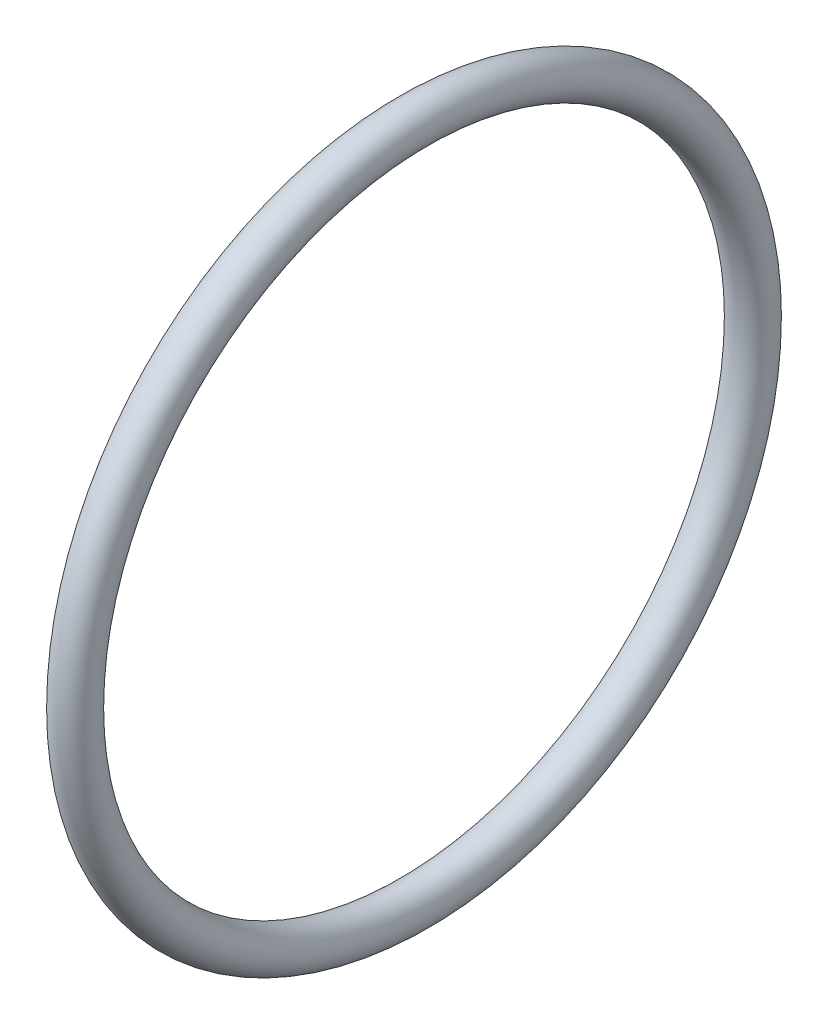
SolidWorks part; units mm, degrees
ref_plane "Front Plane" through (0, 0, 0) normal (0, 0, 1) x (1, 0, 0)
ref_plane "Top Plane" through (0, 0, 0) normal (0, 1, 0) x (1, 0, 0)
ref_plane "Right Plane" through (0, 0, 0) normal (1, 0, 0) x (0, 0, -1)
sketch "Sketch2" plane through (0, 0, 0) normal (0, 0, 1) x (1, 0, 0)
  line L0 (0, 0) -> (58.591, 0) construction
  line L2 (0, 0) -> (18.4, 0)
  line L3 (0, 0) -> (0, 2.5)
  line L4 (0, 2.5) -> (18.4, 2.5)
  line L5 (18.4, 0) -> (18.4, 2.5)
  line L6 (6, 2.5) -> (6, 6)
  line L11 (6, 6) -> (9.97, 6)
  line L16 (12.97, 6) -> (12.97, 3)
  line L17 (12.97, 3) -> (13.6304, 3)
  line L18 (13.6304, 3) -> (13.6304, 2.5)
  line L19 (13.6304, 2.5) -> (6, 2.5)
  line L22 (13.6304, 2.5) -> (16.1104, 2.5)
  line L23 (13.6304, 2.5) -> (13.6304, 4)
  line L24 (13.6304, 4) -> (16.1104, 4)
  line L25 (16.1104, 2.5) -> (16.1104, 4)
  line L27 (6, 6) -> (9.97, 6)
  line L28 (6, 6) -> (6, 9)
  line L29 (6, 9) -> (9.97, 9)
  line L30 (9.97, 6) -> (9.97, 9)
  line L31 (6, 9) -> (6, 8.25)
  line L32 (6, 8.25) -> (5, 8.25)
  line L33 (8.58, 22.001) -> (8.58, 12.476) construction
  line L34 (5, 12.476) -> (12.16, 12.476)
  line L35 (9.97, 9) -> (12.16, 9)
  line L36 (5, 7.5) -> (3, 7.5)
  line L37 (5, 8.25) -> (5, 12.476)
  line L38 (5, 7.5) -> (5, 14)
  line L39 (5, 14) -> (3, 14)
  line L40 (3, 7.5) -> (3, 14)
  line L41 (5, 22.001) -> (12.16, 22.001)
  line L42 (5, 22.001) -> (5, 30.1625)
  line L43 (5, 30.1625) -> (12.16, 30.1625)
  line L44 (12.16, 22.001) -> (12.16, 30.1625)
  line L49 (16.6304, 22.001) -> (16.6304, 7.5)
  line L51 (23.0104, 7.5) -> (23.0104, 6.5)
  line L54 (16.1104, 4) -> (13.6304, 4)
  line L56 (18.0304, 7.5) -> (23.0104, 7.5)
  line L57 (13.16, 22.001) -> (16.6304, 22.001)
  line L58 (16.1104, 3.5) -> (20.0104, 3.5)
  line L59 (29.9004, 14) -> (26.9004, 11)
  line L60 (4, 31.75) -> (18.0304, 31.75)
  line L61 (18.0304, 7.5) -> (23.0104, 7.5)
  line L62 (18.0304, 7.5) -> (18.0304, 12)
  line L63 (18.0304, 12) -> (23.0104, 12)
  line L64 (23.0104, 7.5) -> (23.0104, 12)
  line L65 (18.0304, 31.75) -> (18.0304, 12)
  line L66 (23.0104, 11) -> (26.9004, 11)
  line L67 (34.8004, 23) -> (31.3004, 19.5)
  line L68 (35.8004, 31) -> (38.7904, 33.99)
  line L69 (29.9004, 14) -> (29.9004, 15)
  line L70 (29.9004, 15) -> (22.9304, 15)
  line L71 (22.9304, 15) -> (21.0304, 15)
  line L72 (18.0304, 7.5) -> (16.6304, 7.5)
  line L73 (21.0304, 15) -> (21.0304, 43)
  line L74 (20.0304, 40) -> (10.0704, 40)
  line L75 (10.0704, 40) -> (4, 40)
  line L76 (21.0304, 43) -> (20.0304, 43)
  line L77 (22.9304, 15) -> (29.9004, 15)
  line L78 (22.9304, 15) -> (22.9304, 21)
  line L79 (22.9304, 21) -> (29.9004, 21)
  line L80 (29.9004, 15) -> (29.9004, 21)
  line L81 (10.0704, 40) -> (20.0304, 40)
  line L82 (10.0704, 40) -> (10.0704, 50)
  line L83 (10.0704, 50) -> (20.0304, 50)
  line L84 (20.0304, 40) -> (20.0304, 50)
  line L85 (4, 40) -> (4, 31.75)
  line L86 (12.97, 3) -> (12.97, 2.5)
  line L87 (31.3004, 19.5) -> (29.9004, 19.5)
  line L88 (21.51, 63.5) -> (21.51, 44)
  line L89 (21.51, 63.5) -> (25.9304, 63.5)
  line L90 (25.9304, 63.5) -> (25.9304, 25)
  line L91 (27.8304, 25) -> (25.9304, 25)
  line L92 (10.0704, 48) -> (9, 48)
  line L93 (9, 48) -> (9, 53.476)
  line L94 (9, 53.476) -> (20.0304, 53.476)
  line L95 (20.0304, 53.476) -> (20.0304, 50)
  line L96 (14.5152, 63.001) -> (14.5152, 53.476) construction
  line L97 (9, 63.001) -> (20.0304, 63.001)
  line L98 (9, 63.001) -> (9, 68.2625)
  line L99 (9, 68.2625) -> (20.0304, 68.2625)
  line L100 (20.0304, 63.001) -> (20.0304, 68.2625)
  line L101 (12.97, 6) -> (11.97, 6)
  line L102 (9, 42.5) -> (5, 42.5)
  line L103 (9, 42.5) -> (9, 55)
  line L104 (9, 55) -> (5, 55)
  line L105 (5, 42.5) -> (5, 55)
  line L106 (9.97, 6) -> (10.87, 6)
  line L107 (27.8304, 25) -> (34.8004, 25)
  line L108 (34.8004, 25) -> (34.8004, 23)
  line L109 (0, 0) -> (-2, 0)
  line L110 (0, 0) -> (0, 11)
  line L111 (27.8304, 25) -> (34.8004, 25)
  line L112 (27.8304, 25) -> (27.8304, 32.5)
  line L113 (27.8304, 32.5) -> (34.8004, 32.5)
  line L114 (34.8004, 25) -> (34.8004, 32.5)
  line L115 (35.8004, 31) -> (34.8004, 31)
  line L116 (27.8304, 32.5) -> (27.8304, 64.5)
  line L117 (21.1827, 74.025) -> (6.8477, 74.025)
  line L118 (6.8477, 74.025) -> (6.8477, 76.2)
  line L119 (38.7904, 47.29) -> (30.8304, 55.25)
  line L120 (0, 11) -> (-2, 11)
  line L121 (38.7904, 43.815) -> (30.8529, 43.815)
  line L123 (-4.8, 69.85) -> (1.55, 76.2)
  line L124 (38.7904, 47.29) -> (38.7904, 33.99)
  line L125 (-2, 0) -> (-2, 11)
  line L126 (38.7904, 37.465) -> (30.8529, 37.465)
  line L127 (30.8529, 43.815) -> (30.8529, 37.465)
  line L128 (6, 2.5) -> (6, 0)
  line L129 (0, 63.5) -> (0, 30)
  line L132 (5, 63.5) -> (0, 63.5)
  line L136 (-1.8, 30) -> (-11.76, 30)
  line L138 (-13.76, 25.4) -> (-2, 25.4)
  line L139 (-2, 25.4) -> (-2, 11.5)
  line L140 (27.8304, 64.5) -> (21.1827, 64.5)
  line L141 (-1.8, 30) -> (-11.76, 30)
  line L142 (-1.8, 30) -> (-1.8, 39)
  line L143 (-1.8, 39) -> (-11.76, 39)
  line L144 (-11.76, 30) -> (-11.76, 39)
  line L145 (21.1827, 64.5) -> (21.1827, 74.025)
  line L146 (-12.76, 37) -> (-12.76, 47.29)
  line L147 (-12.76, 37) -> (-11.76, 37)
  line L148 (30.8304, 55.25) -> (30.8304, 76.2)
  line L149 (11.97, 6) -> (11.97, 5.45)
  line L154 (-2, 11.5) -> (1, 11.5)
  line L155 (5, 60.6197) -> (24.05, 60.6197)
  line L160 (5, 60.6197) -> (5, 55.8572)
  line L161 (5, 55.8572) -> (24.05, 55.8572)
  line L166 (24.05, 60.6197) -> (24.05, 55.8572)
  line L167 (5, 60.6197) -> (24.05, 55.8572) construction
  line L172 (5, 55.8572) -> (24.05, 60.6197) construction
  line L173 (24.05, 62.2072) -> (25.9304, 62.2072)
  line L174 (11.97, 5.45) -> (10.87, 5.45)
  line L175 (10.87, 6) -> (10.87, 5.45)
  line L176 (24.05, 62.2072) -> (24.05, 54.2697)
  line L177 (24.05, 54.2697) -> (25.9304, 54.2697)
  line L178 (25.9304, 62.2072) -> (25.9304, 54.2697)
  line L179 (24.05, 62.2072) -> (25.9304, 54.2697) construction
  line L180 (24.05, 54.2697) -> (25.9304, 62.2072) construction
  line L181 (3, 19.6197) -> (15.7, 19.6197)
  line L182 (3, 19.6197) -> (3, 14.8572)
  line L183 (3, 14.8572) -> (15.7, 14.8572)
  line L184 (15.7, 19.6197) -> (15.7, 14.8572)
  line L185 (3, 19.6197) -> (15.7, 14.8572) construction
  line L186 (3, 14.8572) -> (15.7, 19.6197) construction
  line L187 (15.7, 21.2072) -> (16.6304, 21.2072)
  line L188 (15.7, 21.2072) -> (15.7, 13.2697)
  line L189 (15.7, 13.2697) -> (16.6304, 13.2697)
  line L190 (16.6304, 21.2072) -> (16.6304, 13.2697)
  line L191 (15.7, 21.2072) -> (16.6304, 13.2697) construction
  line L192 (15.7, 13.2697) -> (16.6304, 21.2072) construction
  line L193 (1, 11.5) -> (1, 6.5)
  line L194 (1, 6.5) -> (3, 6.5)
  line L195 (23.0104, 6.5) -> (20.0104, 3.5)
  line L196 (5, 63.5) -> (5, 42.5)
  line L197 (5, 42.5) -> (3, 42.5)
  line L198 (3, 42.5) -> (3, 6.5)
  line L199 (6, 0) -> (12.97, 0)
  line L200 (12.97, 0) -> (12.97, 2.5)
  line L201 (18.0304, 31.75) -> (18.0304, 35.875)
  line L202 (18.0304, 35.875) -> (21.0304, 35.875)
  line L203 (30.8304, 76.2) -> (6.8477, 76.2)
  line L204 (3.4027, 69.85) -> (7.8477, 69.85) construction
  line L205 (7.8477, 67.4687) -> (26.8977, 67.4688)
  line L206 (7.8477, 74.025) -> (7.8477, 64.5)
  line L207 (7.8477, 64.5) -> (-1.8, 64.5)
  line L208 (-1.8, 64.5) -> (-1.8, 39)
  line L209 (-12.76, 47.29) -> (-4.8, 55.25)
  line L210 (-4.8, 55.25) -> (-4.8, 69.85)
  line L211 (7.8477, 67.4687) -> (7.8477, 72.2313)
  line L212 (7.8477, 72.2313) -> (26.8977, 72.2313)
  line L213 (26.8977, 67.4688) -> (26.8977, 72.2313)
  line L214 (26.8977, 73.8187) -> (30.8304, 73.8187)
  line L215 (26.8977, 73.8187) -> (26.8977, 65.8813)
  line L216 (26.8977, 65.8813) -> (30.8304, 65.8813)
  line L217 (30.8304, 73.8187) -> (30.8304, 65.8813)
  line L218 (3.4027, 72.2313) -> (25.6277, 72.2313)
  line L219 (3.4027, 72.2313) -> (3.4027, 67.4687)
  line L220 (3.4027, 67.4687) -> (25.6277, 67.4687)
  line L221 (25.6277, 72.2313) -> (25.6277, 67.4687)
  line L222 (25.6277, 69.85) -> (21.1827, 69.85) construction
  line L223 (21.51, 44) -> (22.9304, 44)
  line L224 (22.9304, 44) -> (22.9304, 21)
  line L225 (13.6304, 4) -> (13.6304, 12.2697)
  line L226 (13.6304, 12.2697) -> (13.16, 12.2697)
  line L227 (13.16, 12.2697) -> (13.16, 22.001)
  line L228 (12.16, 9) -> (12.16, 12.476)
  line L229 (-1.8, 30) -> (0, 30)
  line L230 (9, 65.6317) -> (3.4027, 65.6317) construction
  line L231 (20.0304, 65.6317) -> (25.6277, 65.6317) construction
  line L232 (1.55, 76.2) -> (6.8477, 76.2)
  line L233 (-11.76, 30) -> (-13.76, 30)
  line L234 (-13.76, 30) -> (-13.76, 25.4)
  circle A0 centre (26.8804, 25.95) radius 0.95
  circle A1 centre (21.9804, 15.95) radius 0.95
  circle A2 centre (17.3304, 8.2) radius 0.7
  circle A3 centre (10.42, 6.45) radius 0.45
  circle A4 centre (-0.9, 30.9) radius 0.9
  point P7 (24.9902, 58.2385)
  point P131 (16.1652, 17.2385)
  point P135 (14.525, 58.2385)
  point P146 (9.35, 17.2385)
sketch "Sketch3" plane through (0, 0, 0) normal (0, 0, 1) x (1, 0, 0)
  circle A0 centre (21.9804, 15.95) radius 0.95 construction
  circle A1 centre (21.9804, 15.95) radius 0.95
revolve "Revolve1" add sketch "Sketch3" angle 360 about L0
